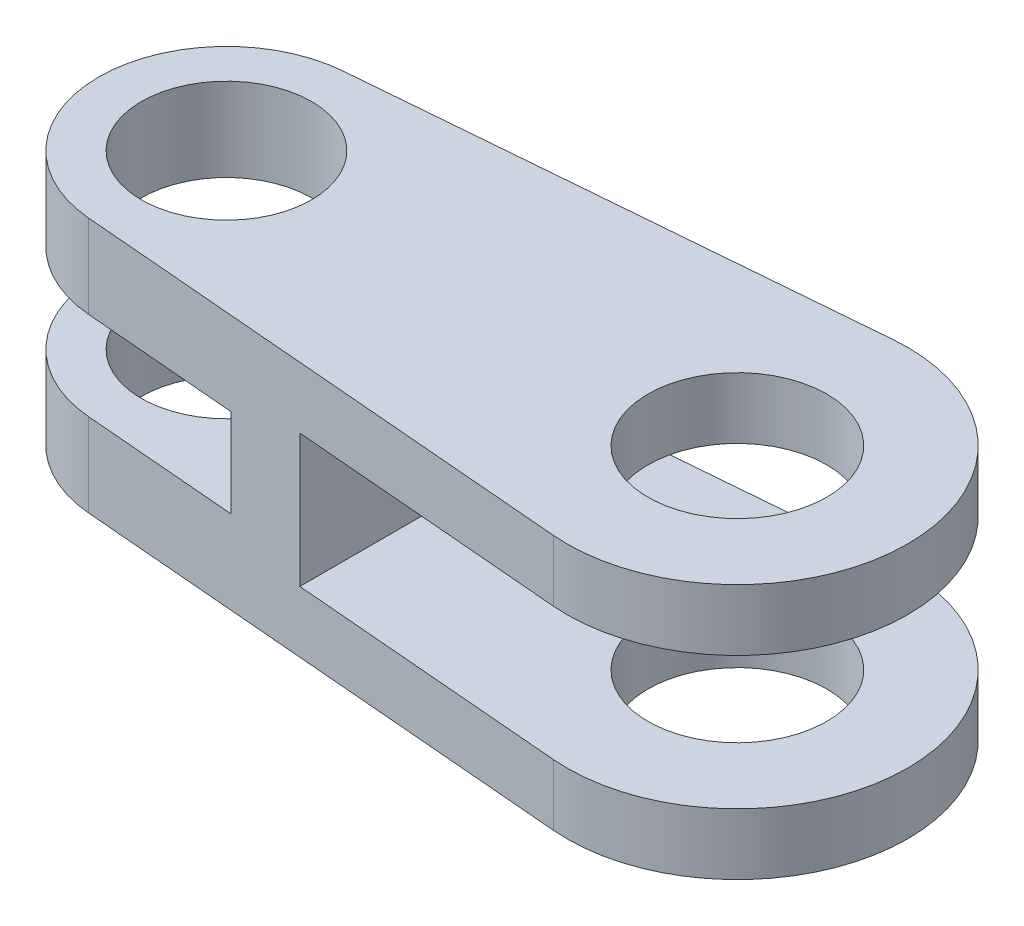
SolidWorks part; units mm, degrees
ref_plane "XY" through (0, 0, 0) normal (0, 0, 1) x (1, 0, 0)
ref_plane "XZ" through (0, 0, 0) normal (0, 1, 0) x (1, 0, 0)
ref_plane "YZ" through (0, 0, 0) normal (1, 0, 0) x (0, 0, -1)
ref_axis "X" through (-13.1762, 0, 0) along (1, 0, 0)
ref_axis "Y" through (0, -10.4775, 0) along (0, 1, 0)
ref_axis "Z" through (0, 0, 13.97) along (0, 0, -1)
sketch "Sketch1" plane through (0, 0, 0) normal (0, 1, 0) x (1, 0, 0)
  line L0 (-0.7937, 9.4919) -> (37.0417, 12.6558)
  line L1 (37.0417, -12.6558) -> (-0.7937, -9.4919)
  line L2 (0, 0) -> (38.1, 0) construction
  arc A0 (37.0417, 12.6558) -> (37.0417, -12.6558) centre (38.1, 0) cw
  arc A1 (-0.7937, -9.4919) -> (-0.7937, 9.4919) centre (0, 0) cw
  circle A3 centre (0, 0) radius 6.35
  circle A4 centre (38.1, 0) radius 6.6675
  dimension "D1" = 9.525
  dimension "D2" = 13.335
  dimension "D3" = 12.7
  dimension "D4" = 12.7
  dimension "D5" = 38.1
extrude "Boss-Extrude1" add sketch "Sketch1" along normal mid plane 19.05
sketch "Sketch2" plane through (0, 0, 0) normal (0, 1, 0) x (1, 0, 0)
  line L0 (37.0417, 12.6558) -> (-0.7937, 9.4919) construction
  line L1 (-10.795, -10.461) -> (10.795, -10.461)
  line L2 (-10.795, -10.461) -> (-10.795, 10.461)
  line L3 (-10.795, 10.461) -> (10.795, 10.461)
  line L4 (10.795, -10.461) -> (10.795, 10.461)
  line L5 (-10.795, -10.461) -> (10.795, 10.461) construction
  line L6 (-10.795, 10.461) -> (10.795, -10.461) construction
  point P0 (0, 0)
  point P7 (0, 0)
  dimension "D1" = 10.795
extrude "Cut-Extrude1" cut sketch "Sketch2" against normal mid plane 6.604
sketch "Sketch3" plane through (0, 0, 0) normal (0, 1, 0) x (1, 0, 0)
  line L0 (0, 0) -> (16.4, 0) construction
  line L1 (37.0417, 12.6558) -> (16.4, 10.9297)
  line L3 (37.0417, -12.6558) -> (16.4, -10.9297)
  line L4 (16.4, 10.9297) -> (16.4, -10.9297)
  line L5 (37.0417, 12.6558) -> (-0.7937, 9.4919) construction
  line L6 (-0.7937, -9.4919) -> (37.0417, -12.6558) construction
  arc A0 (37.0417, -12.6558) -> (37.0417, 12.6558) centre (38.1, 0) ccw construction
  arc A2 (37.0417, -12.6558) -> (37.0417, 12.6558) centre (38.1, 0) ccw
  dimension "D1" = 21.7
extrude "Cut-Extrude2" cut sketch "Sketch3" against normal mid plane 9.906
